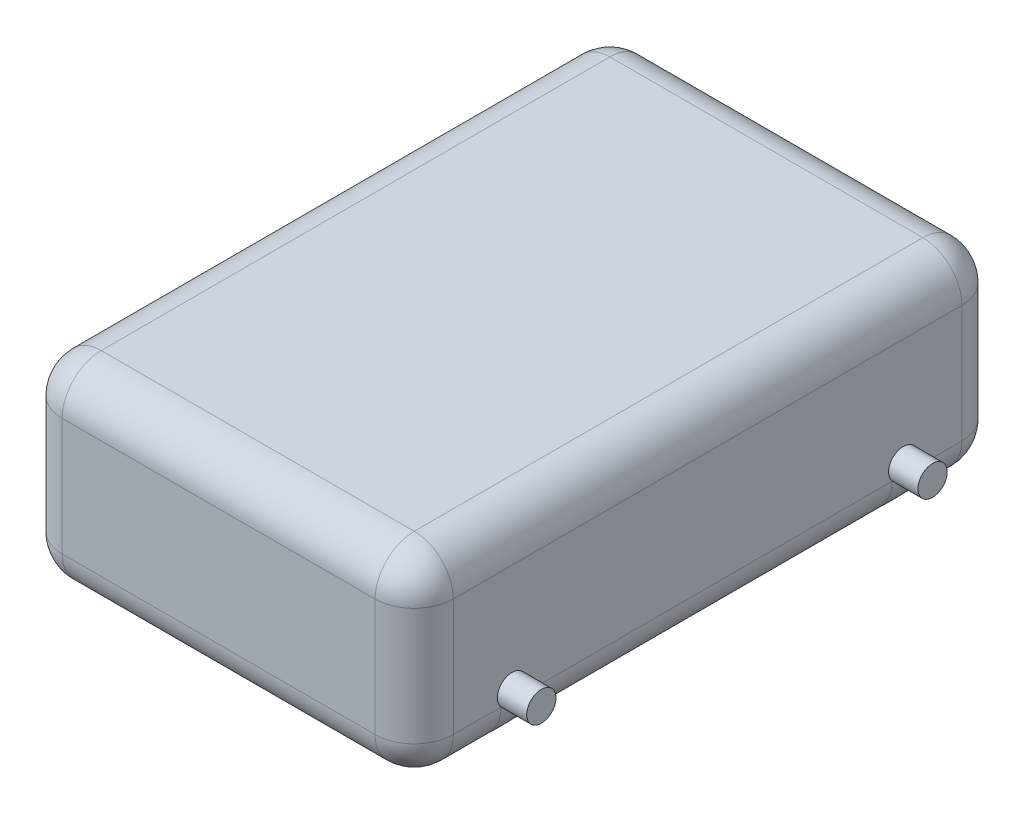
SolidWorks part; units mm, degrees
ref_plane "Front Plane" through (0, 0, 0) normal (0, 0, 1) x (1, 0, 0)
ref_plane "Top Plane" through (0, 0, 0) normal (0, 1, 0) x (1, 0, 0)
ref_plane "Right Plane" through (0, 0, 0) normal (1, 0, 0) x (0, 0, -1)
sketch "Sketch1" plane through (0, 0, 0) normal (0, 1, 0) x (1, 0, 0)
  line L1 (-100, 150) -> (100, 150)
  line L2 (-100, 150) -> (-100, -150)
  line L3 (-100, -150) -> (100, -150)
  line L4 (100, 150) -> (100, -150)
  line L5 (-100, 150) -> (100, -150) construction
  line L6 (-100, -150) -> (100, 150) construction
  point P0 (0, 0)
  dimension "D1" = 300
  dimension "D2" = 200
extrude "Boss-Extrude1" add sketch "Sketch1" along normal blind 100
sketch "Sketch2" plane through (100, 0, 0) normal (1, 0, 0) x (0, 0, -1)
  line L0 (150, 100) -> (150, 0) construction
  line L1 (-150, 0) -> (150, 0) construction
  circle A0 centre (100, 25) radius 7.5
  circle A1 centre (-100, 25) radius 7.5
  dimension "D1" = 15
  dimension "D2" = 50
  dimension "D3" = 25
  dimension "D4" = 50
  dimension "D5" = 25
extrude "Boss-Extrude2" add sketch "Sketch2" along normal blind 15
mirror "Mirror1" about plane through (0, 0, 0) normal (1, 0, 0) of "Boss-Extrude2"
fillet "Fillet1" radius 20 12 edges at (-100, 50, -150) (-100, 50, 150) (0, 0, 150) (100, 0, 0) (0, 0, -150) (-100, 0, 0) (100, 50, -150) (100, 50, 150) (0, 100, 150) (100, 100, 0) (0, 100, -150) (-100, 100, 0)
